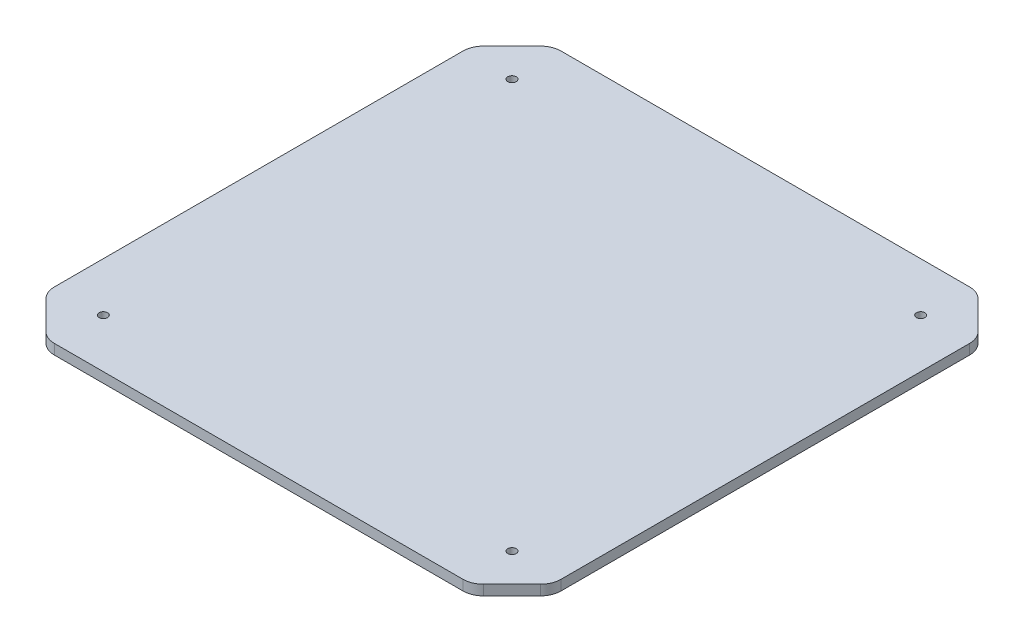
SolidWorks part; units mm, degrees
material "Acrílico (Impacto medio-alto)"
ref_plane "Alzado" through (0, 0, 0) normal (0, 0, 1) x (1, 0, 0)
ref_plane "Planta" through (0, 0, 0) normal (0, 1, 0) x (1, 0, 0)
ref_plane "Vista lateral" through (0, 0, 0) normal (1, 0, 0) x (0, 0, -1)
sketch "Sketch1" plane through (0, 0, 0) normal (0, 1, 0) x (1, 0, 0)
  line L1 (-125, -125) -> (125, -125)
  line L2 (-125, -125) -> (-125, 125)
  line L3 (-125, 125) -> (125, 125)
  line L4 (125, -125) -> (125, 125)
  line L5 (-125, -125) -> (125, 125) construction
  line L6 (-125, 125) -> (125, -125) construction
  point P0 (0, 0)
  dimension "D1" = 250
  dimension "D2" = 250
extrude "Boss-Extrude1" add sketch "Sketch1" along normal blind 5
chamfer "Chamfer1" distance 20 angle 45 4 edges at (125, 2.5, -125) (125, 2.5, 125) (-125, 2.5, 125) (-125, 2.5, -125)
fillet "Fillet2" radius 10 8 edges at (125, 2.5, -105) (105, 2.5, -125) (-125, 2.5, -105) (-105, 2.5, -125) (105, 2.5, 125) (125, 2.5, 105) (-125, 2.5, 105) (-105, 2.5, 125)
sketch "Sketch2" plane through (0, 5, 0) normal (0, 1, 0) x (1, 0, 0)
  line L0 (-100.8579, 100.8579) -> (-100.8579, 125) construction
  line L1 (-100.8579, 100.8579) -> (-125, 100.8579) construction
  line L2 (0, -1000) -> (0, 49000) construction
  line L3 (-1000, 0) -> (49000, 0) construction
  circle A0 centre (-100.8579, 100.8579) radius 2.1
  circle A1 centre (100.8579, 100.8579) radius 2.1
  circle A2 centre (-100.8579, -100.8579) radius 2.1
  circle A3 centre (100.8579, -100.8579) radius 2.1
  dimension "D1" = 4.2
extrude "RF-Hole" cut sketch "Sketch2" against normal through all
